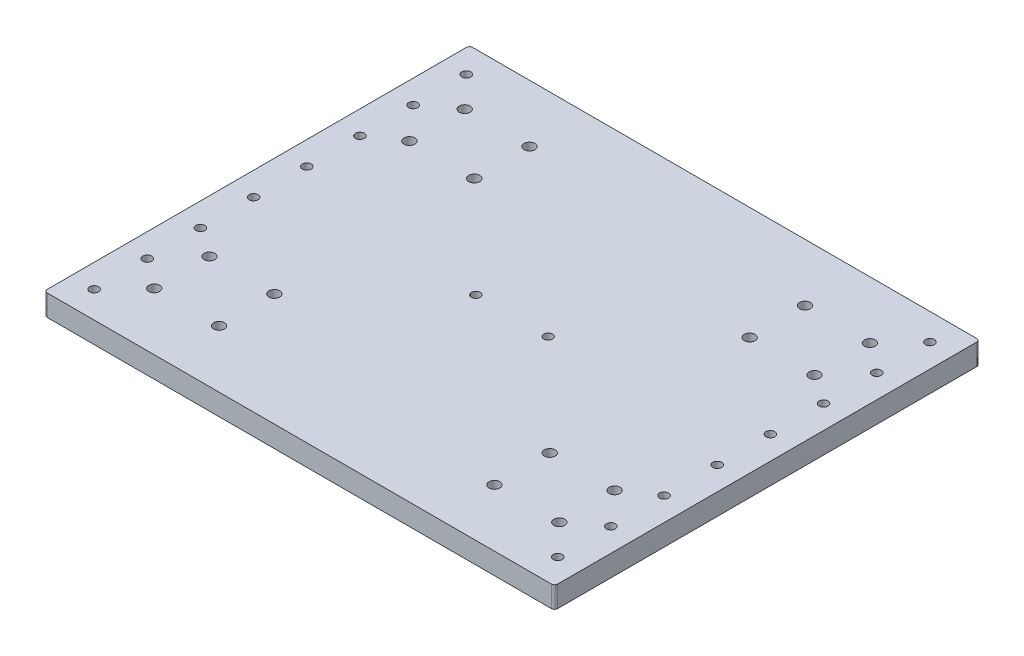
SolidWorks part; units mm, degrees
ref_plane "Front Plane" through (0, 0, 0) normal (0, 0, 1) x (1, 0, 0)
ref_plane "Top Plane" through (0, 0, 0) normal (0, 1, 0) x (1, 0, 0)
ref_plane "Right Plane" through (0, 0, 0) normal (1, 0, 0) x (0, 0, -1)
sketch "Sketch1" plane through (0, 0, 0) normal (0, 1, 0) x (1, 0, 0)
  line L1 (-120, -100) -> (120, -100)
  line L2 (-120, -100) -> (-120, 100)
  line L3 (-120, 100) -> (120, 100)
  line L4 (120, -100) -> (120, 100)
  line L5 (-120, -100) -> (120, 100) construction
  line L6 (-120, 100) -> (120, -100) construction
  point P0 (0, 0)
  dimension "D1" = 240
  dimension "D2" = 200
extrude "Boss-Extrude1" add sketch "Sketch1" along normal mid plane 10
sketch "Sketch2" plane through (0, 5, 0) normal (0, 1, 0) x (1, 0, 0)
  line L5 (-80, 100) -> (-80, -100)
  line L6 (-80, 100) -> (-80, -100) construction
  line L8 (80, -100) -> (80, 100)
  line L9 (80, -100) -> (80, 100) construction
  line L11 (120, 60) -> (-120, 60)
  line L12 (120, 60) -> (-120, 60) construction
  line L14 (-120, -60) -> (120, -60)
  line L15 (-120, -60) -> (120, -60) construction
  line L16 (-95.25, 73) -> (-64.75, 73) construction
  line L17 (-95.25, 73) -> (-95.25, 47) construction
  line L18 (-95.25, 47) -> (-64.75, 47) construction
  line L19 (-64.75, 73) -> (-64.75, 47) construction
  line L20 (-95.25, 73) -> (-64.75, 47) construction
  line L21 (-95.25, 47) -> (-64.75, 73) construction
  line L22 (64.75, 47) -> (95.25, 47) construction
  line L23 (64.75, 47) -> (64.75, 73) construction
  line L24 (64.75, 73) -> (95.25, 73) construction
  line L25 (95.25, 47) -> (95.25, 73) construction
  line L26 (64.75, 47) -> (95.25, 73) construction
  line L27 (64.75, 73) -> (95.25, 47) construction
  line L28 (64.75, -47) -> (95.25, -47) construction
  line L29 (64.75, -47) -> (64.75, -73) construction
  line L30 (64.75, -73) -> (95.25, -73) construction
  line L31 (95.25, -47) -> (95.25, -73) construction
  line L32 (64.75, -47) -> (95.25, -73) construction
  line L33 (64.75, -73) -> (95.25, -47) construction
  line L34 (-95.25, -73) -> (-64.75, -73) construction
  line L35 (-95.25, -73) -> (-95.25, -47) construction
  line L36 (-95.25, -47) -> (-64.75, -47) construction
  line L37 (-64.75, -73) -> (-64.75, -47) construction
  line L38 (-95.25, -73) -> (-64.75, -47) construction
  line L39 (-95.25, -47) -> (-64.75, -73) construction
  circle A0 centre (-95.25, 73) radius 2.55
  circle A1 centre (-95.25, 47) radius 2.55
  circle A2 centre (-64.75, 73) radius 2.55
  circle A3 centre (-64.75, 47) radius 2.55
  circle A4 centre (-95.25, -47) radius 2.55
  circle A5 centre (-95.25, -73) radius 2.55
  circle A6 centre (-64.75, -73) radius 2.55
  circle A7 centre (-64.75, -47) radius 2.55
  circle A8 centre (95.25, -47) radius 2.55
  circle A9 centre (64.75, -47) radius 2.55
  circle A10 centre (64.75, -73) radius 2.55
  circle A11 centre (95.25, -73) radius 2.55
  circle A12 centre (64.75, 73) radius 2.55
  circle A13 centre (64.75, 47) radius 2.55
  circle A14 centre (95.25, 73) radius 2.55
  circle A15 centre (95.25, 47) radius 2.55
  point P0 (-80, 60)
  point P13 (80, 60)
  point P18 (80, -60)
  point P23 (-80, -60)
  dimension "D13" = 5.1
  dimension "D14" = 5.1
  dimension "D15" = 5.1
  dimension "D16" = 5.1
  dimension "D17" = 5.1
  dimension "D18" = 5.1
  dimension "D19" = 5.1
  dimension "D20" = 5.1
  dimension "D21" = 5.1
  dimension "D22" = 5.1
  dimension "D23" = 5.1
  dimension "D24" = 5.1
  dimension "D25" = 5.1
  dimension "D26" = 5.1
  dimension "D27" = 5.1
  dimension "D28" = 5.1
  dimension "D1" = 40
  dimension "D5" = 30.5
  dimension "D6" = 26
  dimension "D7" = 30.5
  dimension "D8" = 26
  dimension "D9" = 26
  dimension "D10" = 30.5
  dimension "D11" = 26
  dimension "D12" = 30.5
  dimension "D2" = 40
  dimension "D3" = 40
  dimension "D4" = 40
extrude "Cut-Extrude1" cut sketch "Sketch2" against normal through all
sketch "Sketch3" plane through (0, 5, 0) normal (0, 1, 0) x (1, 0, 0)
  line L3 (-17, 0) -> (17, 0) construction
  circle A0 centre (-17, 0) radius 2.05
  circle A1 centre (17, 0) radius 2.05
  point P0 (0, 0)
  dimension "D3" = 4.1
  dimension "D4" = 4.1
  dimension "D1" = 34
extrude "Cut-Extrude2" cut sketch "Sketch3" against normal through all
sketch "Sketch4" plane through (0, 5, 0) normal (0, 1, 0) x (1, 0, 0)
  line L0 (-109, 100) -> (-109, -100) construction
  line L1 (120, 100) -> (-120, 100) construction
  line L3 (-120, 100) -> (-120, -100) construction
  line L4 (109, -1000) -> (109, 49000) construction
  line L12 (-120, 100) -> (-120, -100) construction
  line L13 (120, -100) -> (120, 100) construction
  line L14 (-120, 87.5) -> (120, 87.5) construction
  circle A0 centre (-109, 87.5) radius 2.1
  circle A1 centre (109, 87.5) radius 2.1
  point P6 (-120, 0)
  dimension "D3" = 4.2
  dimension "D8" = 4.2
  dimension "D1" = 11
  dimension "D7" = 12.5
  dimension "D6" = 11
extrude "Cut-Extrude3" cut sketch "Sketch4" against normal through all
fillet "Fillet1" radius 1.5 4 edges at (-120, 0, -100) (120, 0, -100) (-120, 0, 100) (120, 0, 100)
pattern_linear "LPattern2" count 8 spacing 25 along (0, 0, 1) of "Cut-Extrude3"
